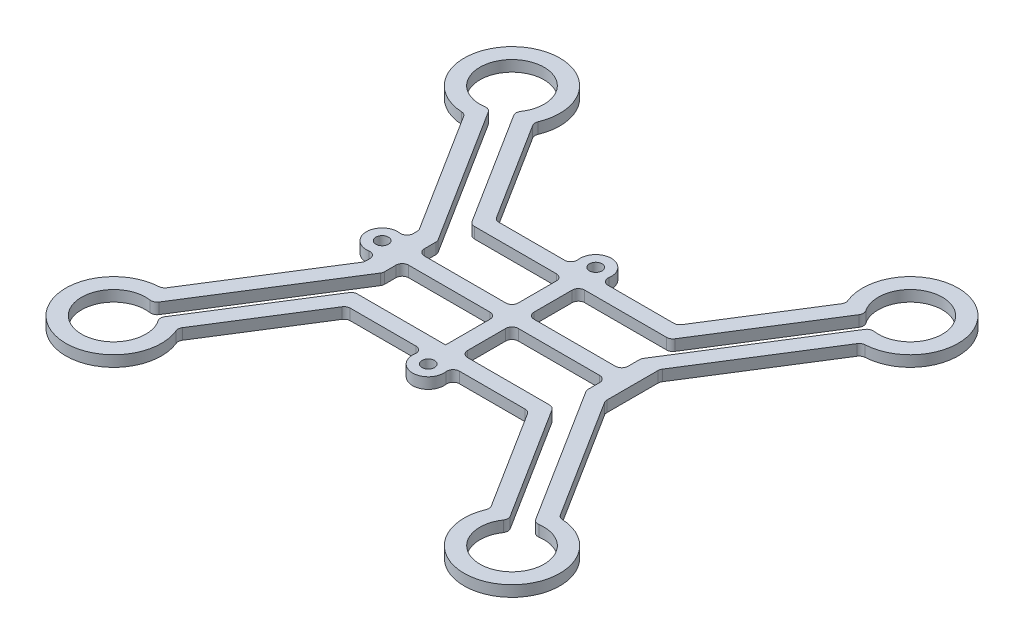
SolidWorks part; units mm, degrees
material "Hexcel AS4C (3000 Filaments)"
ref_plane "Front Plane" through (0, 0, 0) normal (0, 0, 1) x (1, 0, 0)
ref_plane "Top Plane" through (0, 0, 0) normal (0, 1, 0) x (1, 0, 0)
ref_plane "Right Plane" through (0, 0, 0) normal (1, 0, 0) x (0, 0, -1)
sketch "Sketch1" plane through (0, 0, 0) normal (0, 1, 0) x (1, 0, 0)
  line L0 (0, 28.7416) -> (0, -31.95) construction
  line L1 (-19.25, 11.875) -> (19.25, 11.875)
  line L2 (-19.25, 11.875) -> (-19.25, -11.875)
  line L3 (-19.25, -11.875) -> (19.25, -11.875)
  line L4 (19.25, 11.875) -> (19.25, -11.875)
  line L5 (-19.25, 11.875) -> (19.25, -11.875) construction
  line L6 (-19.25, -11.875) -> (19.25, 11.875) construction
  line L7 (-23.7954, 0) -> (45.7192, 0) construction
  line L8 (-31.8198, 4.3198) -> (-31.8198, -4.3198) construction
  line L9 (-31.8198, -31.8198) -> (-31.8198, 31.8198) construction
  line L10 (-31.8198, 31.8198) -> (-19.25, 11.875) construction
  line L11 (19.25, 9.825) -> (-13.5, 9.825)
  line L12 (19.25, 9.825) -> (19.25, -9.825)
  line L13 (19.25, -9.825) -> (-13.5, -9.825)
  line L14 (-13.5, 9.825) -> (-13.5, -9.825)
  line L15 (19.25, 9.825) -> (-13.5, -9.825) construction
  line L16 (19.25, -9.825) -> (-13.5, 9.825) construction
  line L17 (-31.727, 24.1704) -> (-19.25, 4.3728)
  line L18 (-24.959, 28.4358) -> (-14.5219, 11.875)
  line L19 (-35.2038, 29.6871) -> (-22.634, 9.7423) construction
  line L20 (-28.4358, 33.9525) -> (-15.866, 14.0077) construction
  line L21 (24.959, 28.4358) -> (14.5219, 11.875)
  line L22 (31.727, 24.1704) -> (19.25, 4.3728)
  line L23 (24.959, -28.4358) -> (14.5219, -11.875)
  line L24 (31.727, -24.1704) -> (19.25, -4.3728)
  line L25 (-24.959, -28.4358) -> (-14.5219, -11.875)
  line L26 (-31.727, -24.1704) -> (-19.25, -4.3728)
  line L27 (-31.8198, 31.8198) -> (31.8198, 31.8198) construction
  circle A0 centre (-31.8198, 31.8198) radius 27.5
  circle A1 centre (31.8198, 31.8198) radius 27.5
  circle A2 centre (-31.8198, -31.8198) radius 27.5
  circle A3 centre (31.8198, -31.8198) radius 27.5
  circle A4 centre (-31.8198, 31.8198) radius 7.65
  circle A5 centre (-31.8198, 31.8198) radius 5.125
  circle A6 centre (31.8198, 31.8198) radius 5.125
  circle A7 centre (31.8198, 31.8198) radius 7.65
  circle A8 centre (31.8198, -31.8198) radius 5.125
  circle A9 centre (31.8198, -31.8198) radius 7.65
  circle A10 centre (-31.8198, -31.8198) radius 5.125
  circle A11 centre (-31.8198, -31.8198) radius 7.65
  point P0 (0, 0)
  point P18 (2.875, 0)
  dimension "D3" = 55
  dimension "D8" = 15.3
  dimension "D9" = 10.25
  dimension "D1" = 23.75
  dimension "D2" = 38.5
  dimension "D4" = 19.65
  dimension "D5" = 32.75
  dimension "D10" = 8
  dimension "D6" = 90
extrude "Boss-Extrude1" add sketch "Sketch1" along normal blind 1.75 contours A4 A5 | A4 L17 L2 L1 L18 | A11 A10 | L26 A11 L25 L3 L2 | A9 A8 | A9 L24 L4 L3 L23 | A7 A6 | L22 A7 L21 L1 L4 | L26 A2 L2 | A0 L17 L2 | A3 L24 L4 | L22 A1 L12 | L1 L4 L3 L2 region at (-23.128, 0, -17.8619) region at (-19.7311, 0, -6.1292) region at (-27.8564, 0, -25.5309) region at (-19.7311, 0, 6.1292) region at (23.128, 0, -17.8619) region at (-23.128, 0, 17.8619) region at (30.1315, 0, -39.0592) region at (19.7311, 0, -6.1292) region at (-27.8564, 0, 25.5309) region at (19.7311, 0, 6.1292) region at (23.128, 0, 17.8619) region at (27.8564, 0, 25.5309)
sketch "Sketch2" plane through (0, 1.75, 0) normal (0, 1, 0) x (1, 0, 0)
  line L0 (-19.25, 0) -> (19.25, 0) construction
  line L1 (-19.25, 4.3728) -> (-19.25, -4.3728) construction
  line L2 (19.25, 4.3728) -> (19.25, -4.3728) construction
  line L3 (0, 11.875) -> (0, -11.875) construction
  line L4 (-14.5219, 11.875) -> (14.5219, 11.875) construction
  line L5 (-14.5219, -11.875) -> (14.5219, -11.875) construction
  line L6 (-29.0873, 27.484) -> (-11.766, 0) construction
  line L7 (-31.727, 24.1704) -> (-19.25, 4.3728) construction
  line L8 (-24.959, 28.4358) -> (-14.5219, 11.875) construction
  line L9 (-30.4507, 26.881) -> (-16.2654, 4.3728)
  line L10 (-31.8198, 36.9448) -> (-31.8198, 39.4698) construction
  line L11 (-23.3581, 15.6269) -> (-25.4942, 14.2807) construction
  line L12 (-19.25, 4.3728) -> (19.25, 4.3728) construction
  line L13 (-27.955, 28.4539) -> (-12.7784, 4.3728)
  line L14 (-15.9152, 9.35) -> (15.9152, 9.35)
  line L15 (0, 9.35) -> (0, 11.875) construction
  line L16 (-16.2654, 4.3728) -> (-16.2654, -4.3728)
  line L17 (-12.7784, 4.3728) -> (-12.7784, -4.3728)
  line L18 (12.7784, 4.3728) -> (12.7784, -4.3728)
  line L19 (16.2654, 4.3728) -> (16.2654, -4.3728)
  line L20 (27.955, 28.4539) -> (12.7784, 4.3728)
  line L21 (30.4507, 26.881) -> (16.2654, 4.3728)
  line L22 (27.955, -28.4539) -> (12.7784, -4.3728)
  line L23 (30.4507, -26.881) -> (16.2654, -4.3728)
  line L24 (-15.9152, -9.35) -> (15.9152, -9.35)
  line L25 (-30.4507, -26.881) -> (-16.2654, -4.3728)
  line L26 (-27.955, -28.4539) -> (-12.7784, -4.3728)
  line L27 (-1.2625, 0) -> (1.2625, 0) construction
  line L28 (1.2625, -9.35) -> (-1.2625, -9.35)
  line L29 (1.2625, -9.35) -> (1.2625, 9.35)
  line L30 (1.2625, 9.35) -> (-1.2625, 9.35)
  line L31 (-1.2625, -9.35) -> (-1.2625, 9.35)
  line L32 (1.2625, -9.35) -> (-1.2625, 9.35) construction
  line L33 (1.2625, 9.35) -> (-1.2625, -9.35) construction
  line L35 (-16.2654, -1.2625) -> (16.2654, -1.2625)
  line L36 (-16.2654, -1.2625) -> (-16.2654, 1.2625)
  line L37 (-16.2654, 1.2625) -> (16.2654, 1.2625)
  line L38 (16.2654, -1.2625) -> (16.2654, 1.2625)
  line L39 (-16.2654, -1.2625) -> (16.2654, 1.2625) construction
  line L40 (-16.2654, 1.2625) -> (16.2654, -1.2625) construction
  circle A0 centre (-31.8198, 31.8198) radius 5.125 construction
  circle A1 centre (-31.8198, 31.8198) radius 5.125
  circle A2 centre (31.8198, 31.8198) radius 5.125
  arc A3 (-24.959, 28.4358) -> (-31.727, 24.1704) centre (-31.8198, 31.8198) ccw construction
  circle A4 centre (-31.8198, -31.8198) radius 5.125
  circle A5 centre (31.8198, -31.8198) radius 5.125
  point P39 (0, 0)
  point P41 (0, 0)
  point P42 (-16.2654, 0)
  point P45 (12.7784, 0)
  point P47 (0, 9.35)
  point P60 (16.2654, 0)
  point P66 (-12.7784, 0)
extrude "Cut-Extrude2" cut sketch "Sketch2" against normal up to next contours L16 L37 L17 L13 L33 L9 | L17 L37 L31 L14 L13 | L29 L37 L18 L20 L14 | L18 L37 L19 L21 L36 L20 | L35 L18 L22 L23 L19 | L35 L29 L24 L22 L18 | L35 L17 L26 L24 L31 | L35 L16 L25 L32 L26 L17 region at (-20.9447, 1.75, -14.4076) region at (-7.5466, 1.75, -5.4907) region at (-20.9447, 1.75, 14.4076) region at (-7.5466, 1.75, 5.4907) region at (7.5466, 1.75, -5.4907) region at (20.9447, 1.75, -14.4076) region at (7.5466, 1.75, 5.4907) region at (20.9447, 1.75, 14.4076)
fillet "Fillet1" radius 1 43 edges at (-30.4507, 0.875, 26.881) (-31.727, 0.875, -24.1704) (-1.2625, 0.875, -1.2625) (1.2625, 0.875, -1.2625) (-16.2654, 0.875, -1.2625) (-1.2625, 0.875, 1.2625) (-1.2625, 0.875, -9.35) (-31.727, 0.875, 24.1704) (-19.25, 0.875, 4.3728) (-19.25, 0.875, -4.3728) (24.959, 0.875, -28.4358) (-27.955, 0.875, -28.4539) (-27.955, 0.875, 28.4539) (-14.5219, 0.875, -11.875) (-15.9152, 0.875, 9.35) (-30.4507, 0.875, -26.881) (-24.959, 0.875, -28.4358) (-15.9152, 0.875, -9.35) (-16.2654, 0.875, -4.3728) (-16.2654, 0.875, 4.3728) (-16.2654, 0.875, 1.2625) (1.2625, 0.875, -9.35) (1.2625, 0.875, 1.2625) (1.2625, 0.875, 9.35) (16.2654, 0.875, -1.2625) (16.2654, 0.875, -4.3728) (15.9152, 0.875, -9.35) (14.5219, 0.875, -11.875) (30.4507, 0.875, -26.881) (27.955, 0.875, -28.4539) (31.727, 0.875, -24.1704) (19.25, 0.875, -4.3728) (16.2654, 0.875, 1.2625) (16.2654, 0.875, 4.3728) (15.9152, 0.875, 9.35) (19.25, 0.875, 4.3728) (31.727, 0.875, 24.1704) (30.4507, 0.875, 26.881) (27.955, 0.875, 28.4539) (24.959, 0.875, 28.4358) (14.5219, 0.875, 11.875) (-14.5219, 0.875, 11.875) (-24.959, 0.875, 28.4358)
sketch "Sketch4" plane through (0, 0, 0) normal (0, -1, 0) x (1, 0, 0)
  line L0 (-28.6014, 0) -> (31.9252, 0) construction
  line L1 (0, -23.8326) -> (0, 22.253) construction
  line L2 (-13.9701, -11.875) -> (13.9701, -11.875) construction
  line L3 (-0.866, -11.875) -> (-1.7321, -13.375)
  line L4 (-1.7321, -13.375) -> (-0.866, -14.875)
  line L5 (-0.866, -14.875) -> (0.866, -14.875)
  line L6 (0.866, -14.875) -> (1.7321, -13.375)
  line L7 (1.7321, -13.375) -> (0.866, -11.875)
  line L8 (0.866, -11.875) -> (-0.866, -11.875)
  line L9 (-2.5, -13.375) -> (-2.5, -11.875) construction
  line L10 (-20.75, -2.5) -> (-19.25, -2.5) construction
  line L11 (-19.25, -4.084) -> (-19.25, 4.084) construction
  circle A0 centre (0, -13.375) radius 1
  circle A1 centre (0, -13.375) radius 2.5
  circle A2 centre (0, -13.375) radius 1.5 construction
  circle A3 centre (0, 13.375) radius 2.5
  circle A4 centre (0, 13.375) radius 1
  circle A5 centre (-20.75, 0) radius 1
  circle A6 centre (-20.75, 0) radius 2.5
  dimension "D1" = 2
  dimension "D2" = 5
  dimension "D3" = 3
extrude "Boss-Extrude2" add sketch "Sketch4" against normal up to surface (1.75 mm away) contours A6 A5 | A1 L8 L7 L6 L5 L4 L3 | L7 L8 L3 L4 L5 L6 A0 | A3 A4 region at (0, 0, -11.9208) region at (-2.4293, 0, -13.375) region at (-2.4293, 0, 13.375) region at (-23.1793, 0, 0) up to face at (16.0204, 1.75, -12.188)
fillet "Fillet2" radius 1 6 edges at (-2, 0.875, 11.875) (2, 0.875, 11.875) (2, 0.875, -11.875) (-2, 0.875, -11.875) (-19.25, 0.875, -2) (-19.25, 0.875, 2)
equation "\"PropDiameter\"=55"
equation "\"D3@Sketch1\"=\"PropDiameter\""
